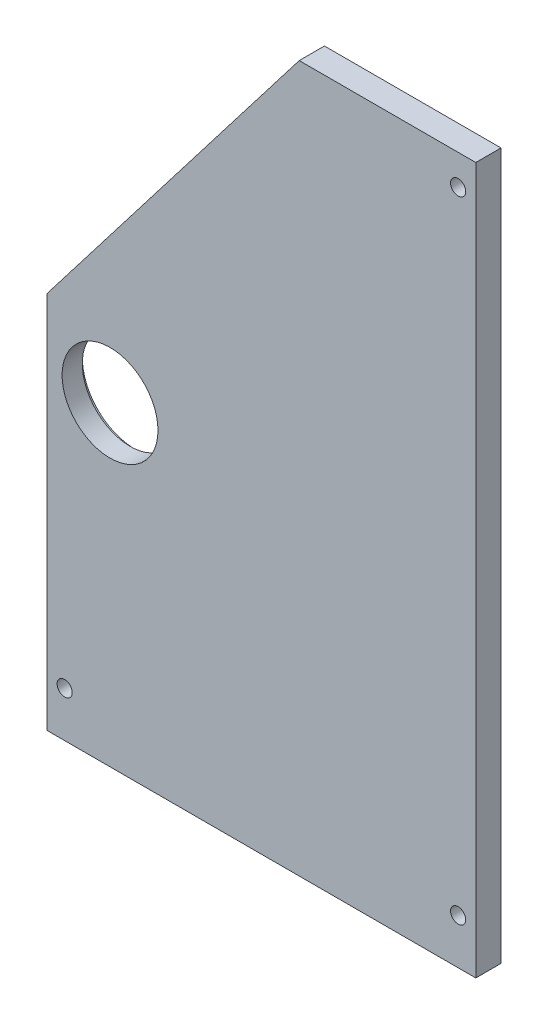
SolidWorks part; units mm, degrees
ref_plane "Front Plane" through (0, 0, 0) normal (0, 0, 1) x (1, 0, 0)
ref_plane "Top Plane" through (0, 0, 0) normal (0, 1, 0) x (1, 0, 0)
ref_plane "Right Plane" through (0, 0, 0) normal (1, 0, 0) x (0, 0, -1)
sketch "Sketch1" plane through (0, 0, 0) normal (0, 0, 1) x (1, 0, 0)
  line L1 (0, 0) -> (50, 0)
  line L2 (0, 0) -> (0, 50) construction
  line L3 (0, 50) -> (50, 50) construction
  line L4 (50, 0) -> (50, 50) construction
  line L5 (0, 0) -> (50, 50) construction
  line L6 (0, 50) -> (50, 0) construction
  line L11 (0, 0) -> (-25, 0)
  line L12 (-25, 0) -> (-25, 75)
  line L13 (-25, 75) -> (50, 75)
  line L14 (0, 50) -> (-25, 75) construction
  line L15 (50, 75) -> (50, 140)
  line L16 (-11.0566, 65) -> (-13.9434, 65) construction
  line L17 (-13.9434, 65) -> (-15.3868, 62.5) construction
  line L18 (-15.3868, 62.5) -> (-13.9434, 60) construction
  line L19 (-13.9434, 60) -> (-11.0566, 60) construction
  line L20 (-11.0566, 60) -> (-9.6132, 62.5) construction
  line L21 (-9.6132, 62.5) -> (-11.0566, 65) construction
  line L22 (53, 140) -> (53, 0) construction
  line L23 (-25, 75) -> (25, 140)
  line L24 (50, 140) -> (60, 140)
  line L25 (60, 140) -> (60, 0)
  line L26 (60, 0) -> (50, 0)
  line L27 (25, 140) -> (50, 140)
  line L28 (72.5, 127.5) -> (60, 127.5)
  line L29 (72.5, 102.5) -> (60, 102.5)
  line L30 (80, 102.5) -> (60, 102.5)
  line L31 (80, 62.5) -> (60, 62.5)
  line L32 (97.9775, 91.264) -> (83.736, 120.4775)
  circle A1 centre (-12.5, 62.5) radius 9.5
  circle A2 centre (-12.5, 62.5) radius 2.5 construction
  circle A3 centre (-12.5, 62.5) radius 5 construction
  circle A4 centre (56.5, 134) radius 1.5
  circle A5 centre (56.5, 9) radius 1.5
  circle A6 centre (-12.5, 62.5) radius 10.5
  circle A7 centre (-21.5, 9) radius 1.5
  circle A8 centre (72.5, 115) radius 9.5
  circle A9 centre (72.5, 115) radius 12.5
  circle A10 centre (72.5, 115) radius 10.5
  circle A11 centre (80, 82.5) radius 12
  circle A13 centre (80, 82.5) radius 20
  circle A14 centre (64, 82.5) radius 1.5
  circle A15 centre (72, 96.3564) radius 1.5
  circle A16 centre (88, 96.3564) radius 1.5
  circle A17 centre (96, 82.5) radius 1.5
  circle A18 centre (88, 68.6436) radius 1.5
  circle A19 centre (72, 68.6436) radius 1.5
  point P4 (25, 25)
  point P6 (25, 25)
  point P63 (80, 82.5)
  dimension "D5" = 19
  dimension "D7" = 10
  dimension "D10" = 3
  dimension "D16" = 3
  dimension "D18" = 21
  dimension "D19" = 3
  dimension "D22" = 19
  dimension "D23" = 25
  dimension "D25" = 21
  dimension "D26" = 24
  dimension "D27" = 3
  dimension "D29" = 40
  dimension "D1" = 50
  dimension "D2" = 50
  dimension "D3" = 75
  dimension "D4" = 75
  dimension "D6" = 5
  dimension "D8" = 65
  dimension "D9" = 10
  dimension "D11" = 3
  dimension "D12" = 3.5
  dimension "D13" = 6
  dimension "D14" = 3.5
  dimension "D15" = 9
  dimension "D17" = 25
  dimension "D20" = 9
  dimension "D21" = 3.5
  dimension "D24" = 25
  dimension "D28" = 16
  dimension "D30" = 6
extrude "Boss-Extrude1" add sketch "Sketch1" along normal blind 5 contours L13 L12 L11 L1 L4 A1 | L26 L25 L24 L15 L4 | L13 L15 region at (22.6807, 42.9919, 0) region at (22.9167, 102.0833, 0)
extrude "Boss-Extrude2" add sketch "Sketch1<3>" against normal blind 4 from surface contours A6 A1 region at (-22.703, 62.5, 0) starting at face at (19, 71, 5)
sketch "Sketch1<3>" plane through (0, 0, 0) normal (0, 0, 1) x (1, 0, 0) same geometry as "Sketch1"
